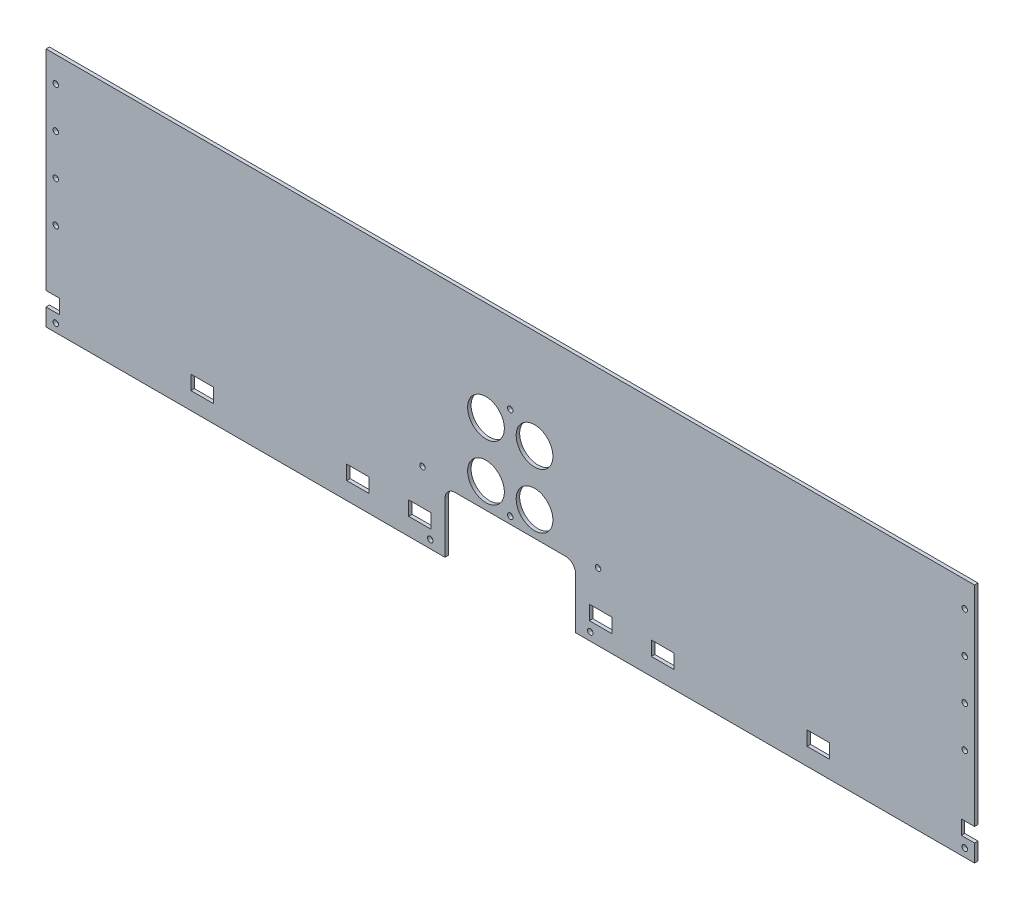
SolidWorks part; units mm, degrees
ref_plane "Front Plane" through (0, 0, 0) normal (0, 0, 1) x (1, 0, 0)
ref_plane "Top Plane" through (0, 0, 0) normal (0, 1, 0) x (1, 0, 0)
ref_plane "Right Plane" through (0, 0, 0) normal (1, 0, 0) x (0, 0, -1)
sketch "Sketch2" plane through (0, 0, 0) normal (0, 1, 0) x (1, 0, 0)
  line L0 (0, 0) -> (0, -85) construction
  line L1 (-30.03, -64.8129) -> (30.03, -64.8129) construction
  line L2 (0, 0) -> (-42.6144, -58.6537) construction
  line L3 (0, 0) -> (-62.7868, -36.25) construction
  line L4 (0, 0) -> (-62.7868, 36.25) construction
  line L5 (-30.03, -64.8129) -> (0, -64.8129)
  arc A0 (34.8348, -63.5829) -> (-34.8348, -63.5829) centre (0, 0) ccw construction
  circle A1 centre (0, -85) radius 38.25 construction
  arc A2 (30.03, -64.8129) -> (34.8348, -63.5829) centre (30.03, -54.8129) ccw
  arc A3 (-30.03, -64.8129) -> (-34.8348, -63.5829) centre (-30.03, -54.8129) cw
  arc A4 (-34.8348, -63.5829) -> (-42.6144, -58.6537) centre (0, 0) cw
  arc A5 (-42.6144, -58.6537) -> (-62.7868, -36.25) centre (0, 0) cw
  arc A6 (-62.7868, -36.25) -> (-62.7868, 36.25) centre (0, 0) cw
  point P8 (32.4891, -64.8129)
  point P16 (-62.8034, 36.2214)
  dimension "D1" = 145
  dimension "D2" = 76.5
  dimension "D4" = 10
  dimension "D3" = 85
  dimension "D5" = 36
  dimension "D6" = 24
  dimension "D7" = 60
sketch "Sketch3" plane through (0, 0, 0) normal (0, 0, 1) x (1, 0, 0)
  line L1 (-227.5, -59) -> (227.5, -59)
  line L2 (-227.5, -59) -> (-227.5, 59)
  line L3 (-227.5, 59) -> (227.5, 59)
  line L4 (227.5, -59) -> (227.5, 59)
  line L5 (-227.5, -59) -> (227.5, 59) construction
  line L6 (-227.5, 59) -> (227.5, -59) construction
  point P0 (0, 0)
  dimension "D1" = 455
  dimension "D2" = 118
extrude "Boss-Extrude2" add sketch "Sketch3" along normal blind 1.7
sketch "Sketch4" plane through (0, 0, 1.7) normal (0, 0, 1) x (1, 0, 0)
  line L0 (0, -59) -> (0, 19.8) construction
  line L1 (-227.5, -59) -> (227.5, -59) construction
  line L2 (227.5, 59) -> (-227.5, 59) construction
  circle A0 centre (0, 19.8) radius 1.35
  circle A1 centre (0, -25.5) radius 1.35
  circle A2 centre (39.2, -55) radius 1.35
  circle A3 centre (43, -26) radius 1.35
  circle A4 centre (222.7, -55) radius 1.35
  circle A5 centre (-222.7, -55) radius 1.35
  circle A6 centre (-43, -26) radius 1.35
  circle A7 centre (-39.2, -55) radius 1.35
  circle A8 centre (222.7, 46.5) radius 1.35
  circle A9 centre (222.7, 26.5) radius 1.35
  circle A10 centre (222.7, 6.5) radius 1.35
  circle A11 centre (222.7, -13.5) radius 1.35
  circle A12 centre (-222.7, -13.5) radius 1.35
  circle A13 centre (-222.7, 6.5) radius 1.35
  circle A14 centre (-222.7, 26.5) radius 1.35
  circle A15 centre (-222.7, 46.5) radius 1.35
  dimension "D1" = 2.7
  dimension "D2" = 78.8
  dimension "D3" = 33.5
  dimension "D4" = 39.2
  dimension "D5" = 4
  dimension "D6" = 43
  dimension "D7" = 33
  dimension "D8" = 222.7
  dimension "D9" = 4
  dimension "D10" = 12.5
  dimension "D12" = 20
  dimension "D11" = 4
extrude "Cut-Extrude1" cut sketch "Sketch4" against normal through all
sketch "Sketch5" plane through (0, 0, 1.7) normal (0, 0, 1) x (1, 0, 0)
  line L0 (-227.5, -59) -> (227.5, -59) construction
  line L1 (-32, -59) -> (32, -59)
  line L2 (-32, -59) -> (-32, -34)
  line L3 (-27, -29) -> (27, -29)
  line L4 (32, -59) -> (32, -34)
  arc A0 (27, -29) -> (32, -34) centre (27, -34) cw
  arc A1 (-32, -34) -> (-27, -29) centre (-27, -34) cw
  point P6 (0, -29)
  point P10 (32, -29)
  dimension "D3" = 5
  dimension "D1" = 64
  dimension "D2" = 30
extrude "Cut-Extrude2" cut sketch "Sketch5" against normal through all
sketch "Sketch6" plane through (0, 0, 1.7) normal (0, 0, 1) x (1, 0, 0)
  line L0 (-227.5, -59) -> (-32, -59) construction
  line L1 (0, 0) -> (0, -29) construction
  line L2 (27, -29) -> (-27, -29) construction
  circle A0 centre (-11.9, -16.75) radius 9
  circle A1 centre (-11.9, 10.25) radius 9
  circle A2 centre (11.9, -16.75) radius 9
  circle A3 centre (11.9, 10.25) radius 9
  point P11 (0, 0)
  dimension "D2" = 18
  dimension "D1" = 42.25
  dimension "D3" = 11.9
  dimension "D4" = 27
extrude "Cut-Extrude3" cut sketch "Sketch6" against normal through all
sketch "Sketch8" plane through (0, 0, 1.7) normal (0, 0, 1) x (1, 0, 0)
  line L0 (-227.5, -59) -> (-32, -59) construction
  line L1 (-49.76, -50.5) -> (-38.76, -50.5)
  line L2 (-49.76, -50.5) -> (-49.76, -43.5)
  line L3 (-49.76, -43.5) -> (-38.76, -43.5)
  line L4 (-38.76, -50.5) -> (-38.76, -43.5)
  line L5 (-49.76, -50.5) -> (-38.76, -43.5) construction
  line L6 (-49.76, -43.5) -> (-38.76, -50.5) construction
  line L7 (0, 0) -> (0, 59) construction
  line L8 (-80.13, -50.5) -> (-69.13, -50.5)
  line L9 (-80.13, -50.5) -> (-80.13, -43.5)
  line L10 (-80.13, -43.5) -> (-69.13, -43.5)
  line L11 (-69.13, -50.5) -> (-69.13, -43.5)
  line L12 (-80.13, -50.5) -> (-69.13, -43.5) construction
  line L13 (-80.13, -43.5) -> (-69.13, -50.5) construction
  line L14 (-156.5, -50.5) -> (-145.5, -50.5)
  line L15 (-156.5, -50.5) -> (-156.5, -43.5)
  line L16 (-156.5, -43.5) -> (-145.5, -43.5)
  line L17 (-145.5, -50.5) -> (-145.5, -43.5)
  line L18 (-156.5, -50.5) -> (-145.5, -43.5) construction
  line L19 (-156.5, -43.5) -> (-145.5, -50.5) construction
  line L20 (-232, -50.5) -> (-221, -50.5)
  line L21 (-232, -50.5) -> (-232, -43.5)
  line L22 (-232, -43.5) -> (-221, -43.5)
  line L23 (-221, -50.5) -> (-221, -43.5)
  line L24 (-232, -50.5) -> (-221, -43.5) construction
  line L25 (-232, -43.5) -> (-221, -50.5) construction
  line L26 (227.5, 59) -> (-227.5, 59) construction
  line L27 (232, -43.5) -> (221, -50.5) construction
  line L28 (232, -50.5) -> (221, -43.5) construction
  line L29 (156.5, -43.5) -> (145.5, -50.5) construction
  line L30 (156.5, -50.5) -> (145.5, -43.5) construction
  line L31 (80.13, -43.5) -> (69.13, -50.5) construction
  line L32 (80.13, -50.5) -> (69.13, -43.5) construction
  line L33 (49.76, -43.5) -> (38.76, -50.5) construction
  line L34 (49.76, -50.5) -> (38.76, -43.5) construction
  line L35 (221, -50.5) -> (221, -43.5)
  line L36 (232, -43.5) -> (221, -43.5)
  line L37 (232, -50.5) -> (232, -43.5)
  line L38 (232, -50.5) -> (221, -50.5)
  line L39 (145.5, -50.5) -> (145.5, -43.5)
  line L40 (156.5, -43.5) -> (145.5, -43.5)
  line L41 (156.5, -50.5) -> (156.5, -43.5)
  line L42 (156.5, -50.5) -> (145.5, -50.5)
  line L43 (69.13, -50.5) -> (69.13, -43.5)
  line L44 (80.13, -43.5) -> (69.13, -43.5)
  line L45 (80.13, -50.5) -> (80.13, -43.5)
  line L46 (80.13, -50.5) -> (69.13, -50.5)
  line L47 (38.76, -50.5) -> (38.76, -43.5)
  line L48 (49.76, -43.5) -> (38.76, -43.5)
  line L49 (49.76, -50.5) -> (49.76, -43.5)
  line L50 (49.76, -50.5) -> (38.76, -50.5)
  point P0 (-44.26, -47)
  point P8 (-74.63, -47)
  point P13 (-151, -47)
  point P18 (-226.5, -47)
  point P43 (226.5, -47)
  point P44 (151, -47)
  point P45 (74.63, -47)
  point P46 (44.26, -47)
  dimension "D1" = 44.26
  dimension "D2" = 11
  dimension "D3" = 7
  dimension "D4" = 12
  dimension "D5" = 74.63
  dimension "D6" = 151
  dimension "D7" = 226.5
extrude "Cut-Extrude4" cut sketch "Sketch8" against normal through all
equation "\"smallPulleyTeeth\"= 30"
equation "\"largePulleyTeeth\"= 30"
equation "\"eighthThick\"= 3.0mm"
equation "\"sixteenthThick\" = 1.7mm"
equation "\"quarterThick\"=6.0mm"
equation "\"OD\" = 145mm"
equation "\"puckAngle\" = 60.5deg"
equation "\"puckDiam\" = 76.5mm"
equation "\"puckDist\" = 85mm"
equation "\"scoopFillet\" = 5mm"
equation "\"axlePress\" = 5.9mm"
equation "\"press\" = 0.2mm"
equation "\"wheelClear\" = 0.3mm"
equation "\"10-32clear\" = 4.8mm"
equation "\"10-32tap\" = 4.45mm"
equation "\"6-32clear\" = 3.3mm"
equation "\"8-32clear\" = 4.0mm"
equation "\"4-40clear\" = 3.0mm"
equation "\"wheelHeight\" = 22mm"
equation "\"wheelWell\" = 65mm"
equation "\"ledSmall\" = 3.1mm"
equation "\"ledLarge\" = 4.2mm"
equation "\"ledLength\" = 4.2mm"
equation "\"4-40close\" = 2.7mm"
equation "\"4-40nutThick\" = 2.2mm"
equation "\"4-40nutWidth\" = 6.2mm"
equation "\"4-40insertHeight\" = 3.5mm"
equation "\"4-40insert\" = 4mm"
equation "\"D1@Boss-Extrude2\"=\"sixteenthThick\""
equation "\"D1@Sketch4\"=\"4-40close\""
equation "\"D1@Sketch2\"=\"OD\""
equation "\"D3@Sketch2\"=\"puckDist\""
